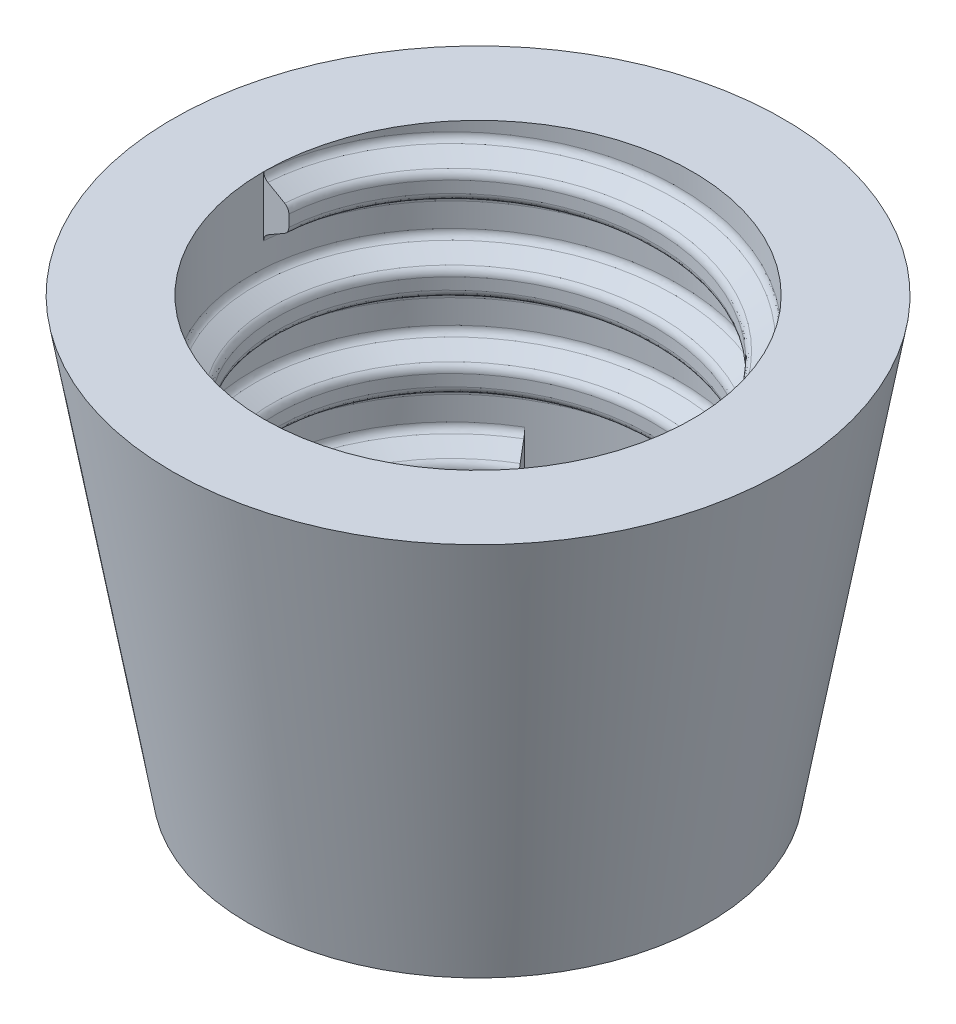
SolidWorks part; units mm, degrees
ref_plane "Front Plane" through (0, 0, 0) normal (0, 0, 1) x (1, 0, 0)
ref_plane "Top Plane" through (0, 0, 0) normal (0, 1, 0) x (1, 0, 0)
ref_plane "Right Plane" through (0, 0, 0) normal (1, 0, 0) x (0, 0, -1)
sketch "Sketch1" plane through (0, 0, 0) normal (0, 1, 0) x (1, 0, 0)
  circle A0 centre (0, 0) radius 15
extrude "Boss-Extrude1" add sketch "Sketch1" along normal blind 20 draft 10 contours A0 draft outward yes
sketch "Sketch2" plane through (0, 20, 0) normal (0, 1, 0) x (1, 0, 0)
  circle A0 centre (0, 0) radius 13
sketch "Sketch10" plane through (0, 20, 0) normal (0, 1, 0) x (1, 0, 0)
  circle A0 centre (0, 0) radius 13
extrude "Cut-Extrude2" cut sketch "Sketch10" against normal blind 20
thread "Thread1" pitch 5.08 method extrude profile "Thread Profile2" start angle 0, offset 0, length 16, pitch 5.08, diameter 26
ref_plane "Plane2" through (-13, 20, 0) normal (0, 0, -1) x (1, 0, 0)
sketch "Thread Profile2" plane through (-13, 20, 0) normal (0, 0, -1) x (1, 0, 0)
  line L0 (0, 0) -> (0, 5.08) construction
  line L1 (0, 0) -> (0, 3.6346)
  line L2 (0.508, 3.6346) -> (1.524, 3.6346) construction
  line L3 (1.524, 2.1681) -> (1.524, 1.4665)
  line L4 (1.27, 2.6081) -> (0.254, 3.1946)
  line L5 (1.27, 1.0265) -> (0.254, 0.4399)
  line L6 (0.508, 0) -> (1.524, 0) construction
  arc A0 (0.254, 3.1946) -> (0, 3.6346) centre (0.508, 3.6346) cw
  arc A1 (0.254, 0.4399) -> (0, 0) centre (0.508, 0) ccw
  arc A2 (1.524, 1.4665) -> (1.27, 1.0265) centre (1.016, 1.4665) cw
  arc A3 (1.524, 2.1681) -> (1.27, 2.6081) centre (1.016, 2.1681) ccw
  point P10 (1.524, 2.4614)
  point P17 (1.524, 1.1732)
  point P18 (0, 3.3413)
  point P19 (0, 0.2933)
  point P20 (0, 0)
  dimension "RootFillet1" = 0.508
  dimension "RootFillet2" = 0.508
  dimension "CrestFillet2" = 0.508
  dimension "CrestFillet1" = 0.508
  dimension "Pitch" = 5.08
  dimension "Angle1" = 30
  dimension "Angle2" = 30
  dimension "a" = 3.048
  dimension "b" = 1.524
  dimension "c" = 1.2882
sketch "Sketch19" plane through (0, 0, 0) normal (0, -1, 0) x (-1, 0, 0)
  circle A0 centre (0, 0) radius 13
  circle A1 centre (0, 0) radius 6.5
sketch "Sketch20" plane through (0, 0, 0) normal (0, -1, 0) x (1, 0, 0)
  circle A0 centre (0, 0) radius 15
extrude "Boss-Extrude3" add sketch "Sketch20" along normal blind 6 draft 10
extrude "Cut-Extrude3" cut sketch "Sketch19" along normal blind 1.5 contours A1
sketch "Sketch47" plane through (0, -1.5, 0) normal (0, 1, 0) x (1, 0, 0)
  circle A0 centre (0, 0) radius 0.5
extrude "Cut-Extrude10" cut sketch "Sketch47" against normal blind 4.5
sketch "Sketch49" plane through (0, -1.5, 0) normal (0, 1, 0) x (1, 0, 0)
  circle A0 centre (0, 0) radius 0.5
  circle A2 centre (1.67, 0) radius 0.5
sketch "Sketch50" plane through (0, -1.5, 0) normal (0, 1, 0) x (1, 0, 0)
  circle A0 centre (3.33, 0) radius 0.5
sketch "Sketch51" plane through (0, -1.5, 0) normal (0, 1, 0) x (1, 0, 0)
  circle A0 centre (5, 0) radius 0.5
extrude "Cut-Extrude13" cut sketch "Sketch49" against normal blind 4.5
extrude "Cut-Extrude14" cut sketch "Sketch50" against normal blind 4.5
extrude "Cut-Extrude15" cut sketch "Sketch51" against normal blind 4.5
pattern_circular "CirPattern1" count 18 over 360 about axis through (0, -1.5, 0) along (0, 1, 0) of "Cut-Extrude15"
pattern_circular "CirPattern2" count 12 over 360 about axis through (0, -1.5, 0) along (0, 1, 0) of "Cut-Extrude14"
pattern_circular "CirPattern3" count 6 over 360 about axis through (0, -1.5, 0) along (0, 1, 0) of "Cut-Extrude13"
sketch "Sketch52" plane through (0, -6, 0) normal (0, -1, 0) x (-1, 0, 0)
  circle A0 centre (0, 0) radius 15
